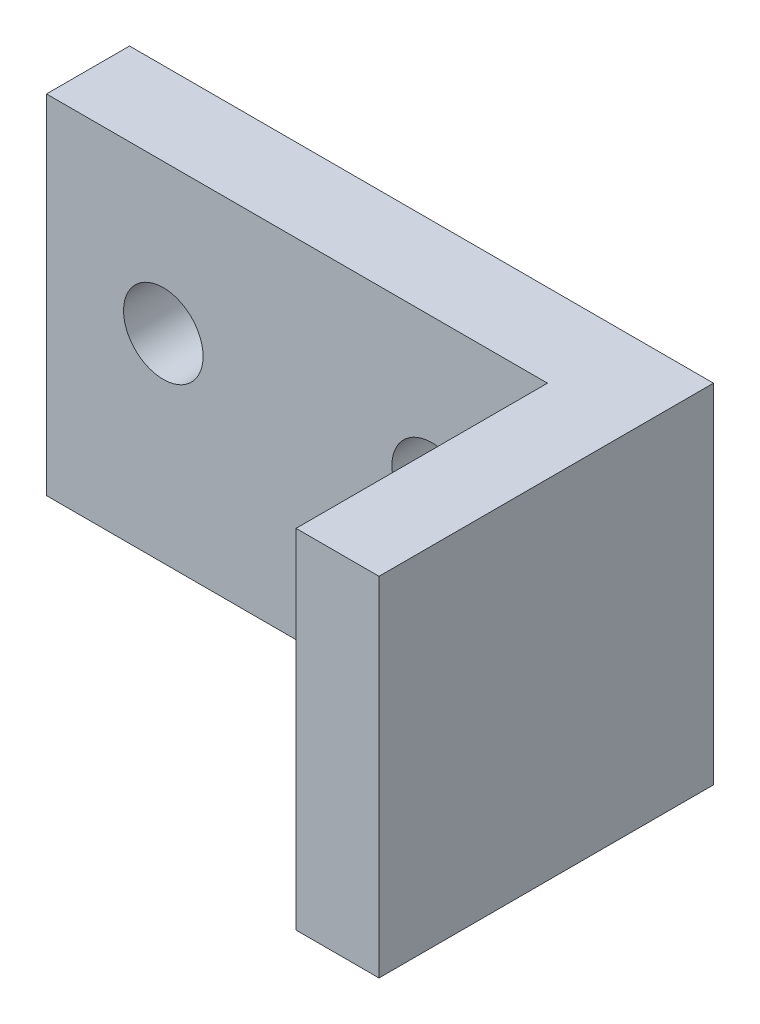
SolidWorks part; units mm, degrees
ref_plane "Ebene vorne" through (0, 0, 0) normal (0, 0, 1) x (1, 0, 0)
ref_plane "Ebene oben" through (0, 0, 0) normal (0, 1, 0) x (1, 0, 0)
ref_plane "Ebene rechts" through (0, 0, 0) normal (1, 0, 0) x (0, 0, -1)
sketch "Skizze1" plane through (0, 0, 0) normal (0, 1, 0) x (1, 0, 0)
  line L1 (-12.6, 12.65) -> (25.15, 12.65)
  line L2 (25.15, 12.65) -> (25.15, -12.65)
  line L3 (25.15, -12.65) -> (-12.6, -12.65)
  line L5 (-12.6, 10.85) -> (23.35, 10.85)
  line L6 (23.35, 10.85) -> (23.35, -10.85)
  line L7 (23.35, -10.85) -> (-12.6, -10.85)
  arc A0 (-12.6, 12.65) -> (-12.6, -12.65) centre (-12.6, 0) ccw
  arc A1 (-12.6, 10.85) -> (-12.6, -10.85) centre (-12.6, 0) ccw
sketch "Skizze2" plane through (0, 0, 0) normal (0, 0, 1) x (1, 0, 0)
  line L0 (0, 170) -> (0, 570)
sketch "Skizze3" plane through (0, 0, 0) normal (0, 0, 1) x (1, 0, 0)
  line L13 (-11, 155) -> (11, 155)
  line L15 (11, 155) -> (11, 130)
  line L17 (11, 130) -> (33.5, 130)
  line L18 (33.5, 130) -> (33.5, 205)
  line L19 (33.5, 205) -> (-33.5, 205)
  line L23 (-33.5, 130) -> (-33.5, 205)
  line L24 (-11, 130) -> (-33.5, 130)
  line L25 (-11, 155) -> (-11, 130)
  point P16 (0, 205)
  point P19 (0, 155)
sketch "Skizze4" plane through (0, 0, 0) normal (0, 1, 0) x (1, 0, 0)
  line L0 (25.15, -12.65) -> (33.5, -12.65)
  line L1 (33.5, -12.65) -> (33.5, 21)
  line L2 (33.5, 21) -> (-25.25, 21)
  line L3 (25.15, -12.65) -> (25.15, 12.65)
  line L4 (25.15, 12.65) -> (-25.25, 12.65)
  line L5 (-25.25, 12.65) -> (-25.25, 21)
extrude "Aufsatz-Linear austragen1" add sketch "Skizze4" along normal up to vertex (205 mm away) from vertex up to point (33.5, 205, 0) starting at point (0, 170, 0)
sketch "Holes" plane through (0, 0, 0) normal (0, 0, 1) x (1, 0, 0)
  circle A0 centre (13.5, 190) radius 4
  circle A1 centre (-13.5, 190) radius 4
sketch "Skizze6" plane through (0, 0, 0) normal (0, 0, 1) x (1, 0, 0)
  circle A0 centre (-13.5, 190) radius 4
  circle A1 centre (13.5, 190) radius 4
extrude "Schnitt-Linear austragen1" cut sketch "Skizze6" against normal up to surface (21 mm away) up to face at (4.125, 187.5, -21)
